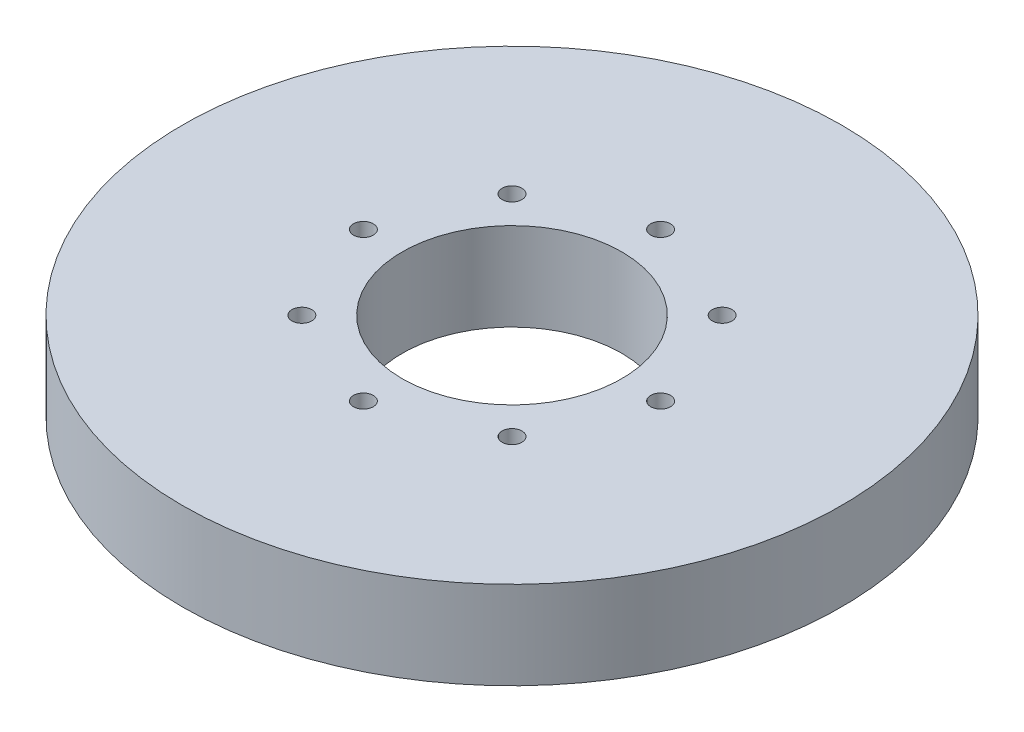
SolidWorks part; units mm, degrees
ref_plane "Front Plane" through (0, 0, 0) normal (0, 0, 1) x (1, 0, 0)
ref_plane "Top Plane" through (0, 0, 0) normal (0, 1, 0) x (1, 0, 0)
ref_plane "Right Plane" through (0, 0, 0) normal (1, 0, 0) x (0, 0, -1)
sketch "Sketch1" plane through (0, 0, 0) normal (0, 1, 0) x (1, 0, 0)
  circle A0 centre (0, 0) radius 82.5
  dimension "FLANGE_OD" = 165
extrude "Boss-Extrude1" add sketch "Sketch1" along normal blind 22
sketch "Sketch2" plane through (0, 0, 0) normal (0, 1, 0) x (1, 0, 0)
  circle A0 centre (0, 0) radius 27.5
  dimension "BORE_D" = 55
extrude "Cut-Extrude1" cut sketch "Sketch2" along normal through all
sketch "Sketch3" plane through (0, 22, 0) normal (0, 1, 0) x (1, 0, 0)
  circle A0 centre (0, 0) radius 37.2028 construction
  circle A1 centre (-37.2028, 0) radius 2.4739
  dimension "BOLT_D" = 4.9477
  dimension "BOLT_PCD" = 74.4056
extrude "Cut-Extrude2" cut sketch "Sketch3" against normal blind 18.7042
pattern_circular "CirPattern1" count 8 over 360 about axis through (0, 0, 0) along (0, 1, 0) of "Cut-Extrude2"
